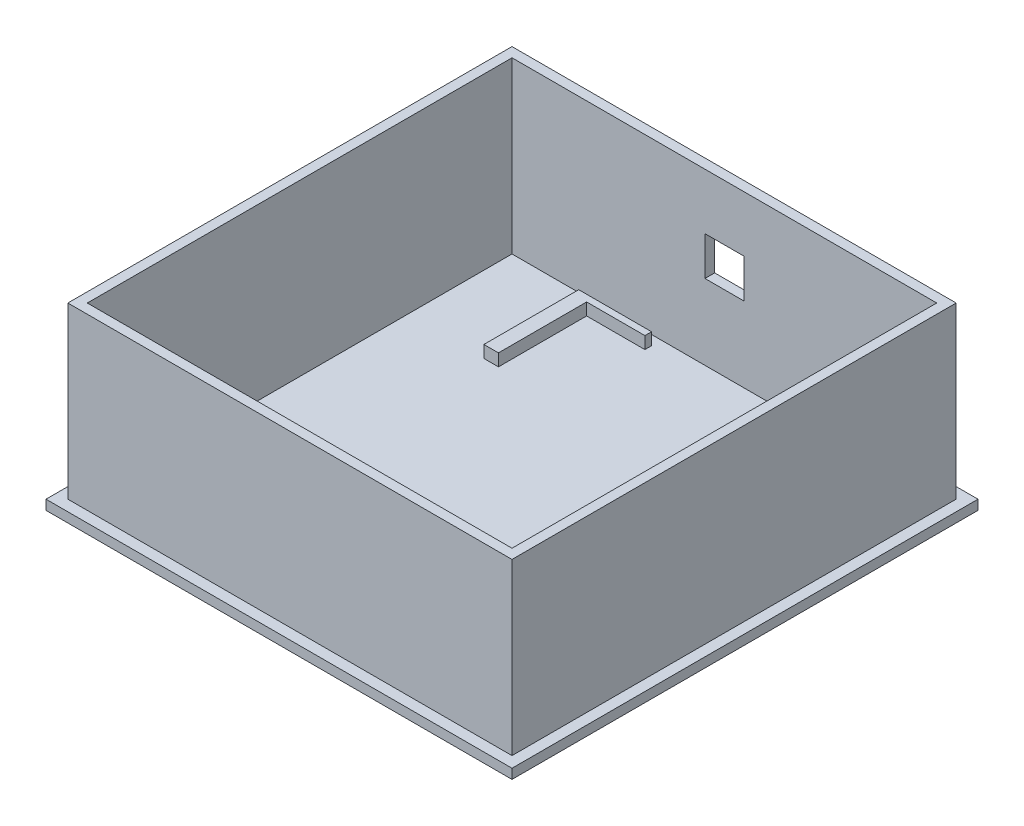
SolidWorks part; units mm, degrees
ref_plane "Front Plane" through (0, 0, 0) normal (0, 0, 1) x (1, 0, 0)
ref_plane "Top Plane" through (0, 0, 0) normal (0, 1, 0) x (1, 0, 0)
ref_plane "Right Plane" through (0, 0, 0) normal (1, 0, 0) x (0, 0, -1)
sketch "Sketch1" plane through (0, 0, 0) normal (0, 1, 0) x (1, 0, 0)
  line L1 (-50, -50) -> (50, -50)
  line L2 (-50, -50) -> (-50, 50)
  line L3 (-50, 50) -> (50, 50)
  line L4 (50, -50) -> (50, 50)
  line L5 (-50, -50) -> (50, 50) construction
  line L6 (-50, 50) -> (50, -50) construction
  point P0 (0, 0)
  dimension "D1" = 100
extrude "Boss-Extrude1" add sketch "Sketch1" along normal blind 4
sketch "Sketch2" plane through (0, 4, 0) normal (0, 1, 0) x (1, 0, 0)
  line L4 (41.75, -41.75) -> (41.75, 41.75)
  line L5 (41.75, 41.75) -> (-41.75, 41.75)
  line L6 (-41.75, 41.75) -> (-41.75, -41.75)
  line L7 (-41.75, -41.75) -> (41.75, -41.75)
  line L8 (45.75, -45.75) -> (45.75, 45.75)
  line L9 (45.75, 45.75) -> (-45.75, 45.75)
  line L10 (-45.75, 45.75) -> (-45.75, -45.75)
  line L11 (-45.75, -45.75) -> (45.75, -45.75)
  line L12 (45.75, -45.75) -> (45.75, 45.75)
  line L13 (45.75, 45.75) -> (-45.75, 45.75)
  line L14 (-45.75, 45.75) -> (-45.75, -45.75)
  line L15 (-45.75, -45.75) -> (45.75, -45.75)
  dimension "D1" = 4.25
  dimension "D2" = 4
extrude "Boss-Extrude2" add sketch "Sketch2" along normal blind 35
sketch "Sketch3" plane through (0, 0, -45.75) normal (0, 0, -1) x (-1, 0, 0)
  line L0 (-50, 4) -> (50, 4) construction
  line L1 (-2, 8) -> (2, 8)
  line L2 (-2, 8) -> (-2, 4)
  line L3 (-2, 4) -> (2, 4)
  line L4 (2, 8) -> (2, 4)
  line L5 (-2, 8) -> (2, 4) construction
  line L6 (-2, 4) -> (2, 8) construction
  point P0 (0, 6)
  dimension "D1" = 4
extrude "Cut-Extrude1" cut sketch "Sketch3" against normal up to surface (4 mm away) up to face at (0, 21.5, -41.75)
sketch "Sketch4" plane through (0, 4, 0) normal (0, 1, 0) x (1, 0, 0)
  line L0 (41.75, 41.75) -> (-41.75, 41.75) construction
  line L1 (-25, -39) -> (25, -39)
  line L2 (-25, -39) -> (-25, 39)
  line L3 (-25, 39) -> (25, 39)
  line L4 (25, -39) -> (25, 39)
  line L5 (-25, -39) -> (25, 39) construction
  line L6 (-25, 39) -> (25, -39) construction
  line L7 (-13, 22.21) -> (-28, 22.21)
  line L8 (-13, 22.21) -> (-13, 41.75)
  line L9 (-13, 41.75) -> (-28, 41.75)
  line L10 (-28, 22.21) -> (-28, 41.75)
  line L11 (-13, 22.21) -> (-28, 41.75) construction
  line L12 (-13, 41.75) -> (-28, 22.21) construction
  line L13 (-41.75, -41.75) -> (41.75, -41.75) construction
  line L14 (13, 22.21) -> (28, 22.21)
  line L15 (13, 22.21) -> (13, 41.75)
  line L16 (13, 41.75) -> (28, 41.75)
  line L17 (28, 22.21) -> (28, 41.75)
  line L18 (13, 22.21) -> (28, 41.75) construction
  line L19 (13, 41.75) -> (28, 22.21) construction
  line L20 (-28, -22.21) -> (-13, -22.21)
  line L21 (-28, -22.21) -> (-28, -41.75)
  line L22 (-28, -41.75) -> (-13, -41.75)
  line L23 (-13, -22.21) -> (-13, -41.75)
  line L24 (-28, -22.21) -> (-13, -41.75) construction
  line L25 (-28, -41.75) -> (-13, -22.21) construction
  line L27 (28, -22.21) -> (13, -22.21)
  line L28 (28, -22.21) -> (28, -41.75)
  line L29 (28, -41.75) -> (13, -41.75)
  line L30 (13, -22.21) -> (13, -41.75)
  line L31 (28, -22.21) -> (13, -41.75) construction
  line L32 (28, -41.75) -> (13, -22.21) construction
  point P0 (0, 0)
  point P6 (-20.5, 31.98)
  point P13 (20.5, 31.98)
  point P18 (-20.5, -31.98)
  point P25 (20.5, -31.98)
  line M17 (-41.75, -41.75) -> (41.75, -41.75)
  line M19 (41.75, 41.75) -> (2, 41.75)
  line M27 (-2, 41.75) -> (-41.75, 41.75)
  dimension "D1" = 78
  dimension "D2" = 50
  dimension "D3" = 3
  dimension "D4" = 15
extrude "Boss-Extrude3" add sketch "Sketch4" along normal blind 2.5 contours L10 L7 L2 L3 L8 M27 | L14 L17 L15 L3 L4 M19 | L1 L30 L28 L27 L4 M17 | L23 L1 L2 L20 L21 M17 region at (-19, 4, 39.2463) region at (19, 4, 39.2463) region at (-26.5, 4, -22.4563) region at (25.2463, 4, -30.605)
sketch "Sketch5" plane through (0, 4, 0) normal (0, 1, 0) x (1, 0, 0)
  line L1 (-25, 39) -> (25, 39)
  line L2 (-25, 39) -> (-25, 40.375)
  line L3 (-25, 40.375) -> (25, 40.375)
  line L4 (25, 39) -> (25, 40.375)
  dimension "D1" = 1.375
extrude "Cut-Extrude2" cut sketch "Sketch5" along normal through all
sketch "Sketch6" plane through (0, 0, -45.75) normal (0, 0, -1) x (-1, 0, 0)
  line L0 (-45.75, 4) -> (-2, 4) construction
  line L1 (-4, 19.5) -> (4, 19.5)
  line L2 (-4, 19.5) -> (-4, 27.5)
  line L3 (-4, 27.5) -> (4, 27.5)
  line L4 (4, 19.5) -> (4, 27.5)
  line L5 (-4, 19.5) -> (4, 27.5) construction
  line L6 (-4, 27.5) -> (4, 19.5) construction
  point P0 (0, 23.5)
  dimension "D1" = 15.5
  dimension "D2" = 8
  dimension "D3" = 0
  dimension "D4" = 8
extrude "Cut-Extrude4" cut sketch "Sketch6" against normal blind 12
sketch "Sketch7" plane through (0, 0, -45.75) normal (0, 0, -1) x (-1, 0, 0)
  line L1 (-2, 8) -> (2, 8)
  line L2 (-2, 8) -> (-2, 4)
  line L3 (-2, 4) -> (2, 4)
  line L4 (2, 8) -> (2, 4)
extrude "Boss-Extrude5" add sketch "Sketch7" against normal blind 4
sketch "Sketch8" plane through (0, 39, 0) normal (0, 1, 0) x (1, 0, 0)
  line L0 (45.75, 45.75) -> (-45.75, 45.75) construction
  line L1 (-43.7452, 43.75) -> (43.75, 43.75)
  line L2 (-43.7452, 43.75) -> (-43.7452, -43.75)
  line L3 (-43.7452, -43.75) -> (43.75, -43.75)
  line L4 (43.75, 43.75) -> (43.75, -43.75)
  line L5 (45.75, -45.75) -> (45.75, 45.75) construction
  line L6 (-45.75, -45.75) -> (45.75, -45.75) construction
  line L7 (-45.75, 45.75) -> (-45.75, -45.75) construction
  dimension "D1" = 2
  dimension "D2" = 2
  dimension "D3" = 2
  dimension "D4" = 2.0048
extrude "Cut-Extrude6" cut sketch "Sketch8" against normal up to surface (32.5 mm away) up to face at (-22, 6.5, 34.32)
sketch "Sketch10" plane through (0, 6.5, 0) normal (0, 1, 0) x (1, 0, 0)
  line L1 (-43.7452, 43.75) -> (43.75, 43.75)
  line L2 (-43.7452, 43.75) -> (-43.7452, -43.75)
  line L3 (-43.7452, -43.75) -> (43.75, -43.75)
  line L4 (43.75, 43.75) -> (43.75, -43.75)
  line L5 (-41.75, 41.75) -> (41.75, 41.75)
  line L6 (-41.75, 41.75) -> (-41.75, -41.75)
  line L7 (-41.75, -41.75) -> (41.75, -41.75)
  line L8 (41.75, 41.75) -> (41.75, -41.75)
extrude "Cut-Extrude8" cut sketch "Sketch10" against normal up to surface (2.5 mm away) contours L2 L1 L4 L3 | L6 L5 L8 L7 up to face at (0, 4, -0.1964)
sketch "Sketch11" plane through (0, 4, 0) normal (0, 1, 0) x (1, 0, 0)
  line L0 (-50, 50) -> (-50, -50) construction
  line L1 (-48, 48) -> (48, 48)
  line L2 (-48, 48) -> (-48, -48)
  line L3 (-48, -48) -> (48, -48)
  line L4 (48, 48) -> (48, -48)
  line L5 (50, 50) -> (-50, 50) construction
  line L6 (50, -50) -> (50, 50) construction
  line L7 (-50, -50) -> (50, -50) construction
  dimension "D1" = 2
  dimension "D2" = 2
  dimension "D3" = 2
  dimension "D4" = 2
extrude "Cut-Extrude9" cut sketch "Sketch11" against normal blind 32 flip side to cut
sketch "Sketch12" plane through (0, 0, -48) normal (0, 0, -1) x (-1, 0, 0)
  line L0 (48, 0) -> (48, 4) construction
  line L1 (-48, 0) -> (48, 0)
  line L2 (-48, 0) -> (-48, 2)
  line L3 (-48, 2) -> (48, 2)
  line L4 (48, 0) -> (48, 2)
extrude "Cut-Extrude10" cut sketch "Sketch12" against normal through all
